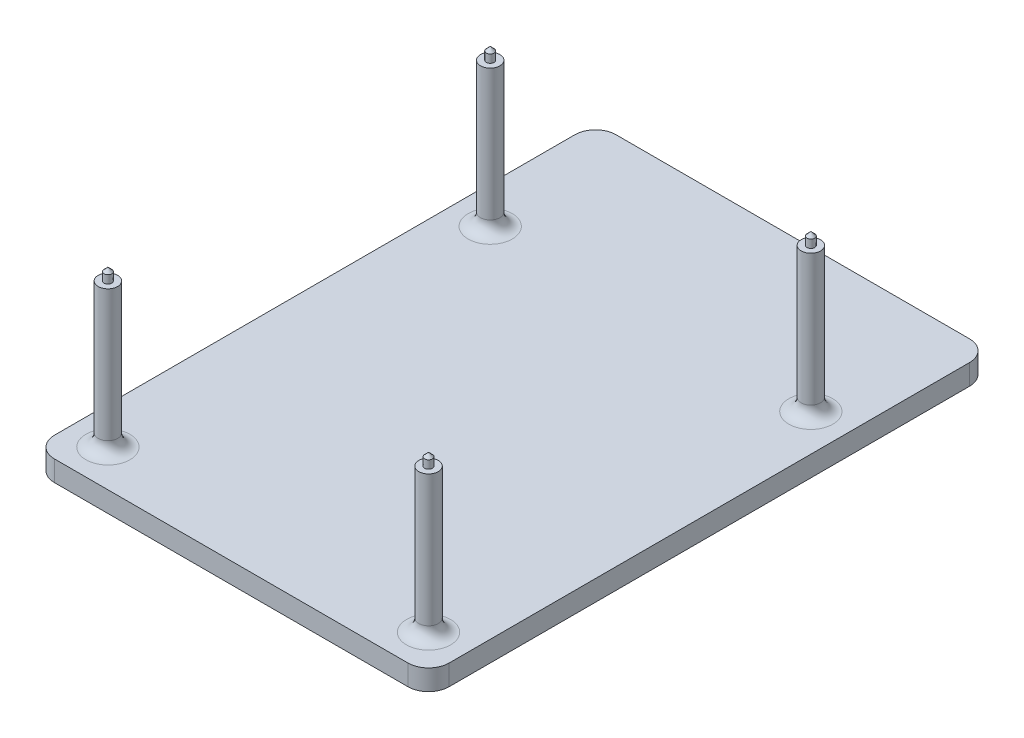
SolidWorks part; units mm, degrees
ref_plane "Front Plane" through (0, 0, 0) normal (0, 0, 1) x (1, 0, 0)
ref_plane "Top Plane" through (0, 0, 0) normal (0, 1, 0) x (1, 0, 0)
ref_plane "Right Plane" through (0, 0, 0) normal (1, 0, 0) x (0, 0, -1)
sketch "Sketch1" plane through (0, 0, 0) normal (0, 1, 0) x (1, 0, 0)
  line L0 (0, 160.782) -> (109.22, 0) construction
  line L1 (5.08, 123.19) -> (104.14, 123.19) construction
  line L2 (5.08, 123.19) -> (5.08, 5.08) construction
  line L3 (5.08, 5.08) -> (104.14, 5.08) construction
  line L4 (104.14, 123.19) -> (104.14, 5.08) construction
  line L5 (0, 0) -> (109.22, 0) construction
  line L6 (0, 0) -> (0, 160.782) construction
  line L7 (0, 160.782) -> (109.22, 160.782) construction
  line L8 (109.22, 0) -> (109.22, 160.782) construction
  line L10 (115.57, 167.132) -> (-6.35, 167.132)
  line L11 (115.57, 167.132) -> (115.57, -6.35)
  line L12 (115.57, -6.35) -> (-6.35, -6.35)
  line L13 (-6.35, 167.132) -> (-6.35, -6.35)
  line L14 (115.57, 167.132) -> (-6.35, -6.35) construction
  line L15 (115.57, -6.35) -> (-6.35, 167.132) construction
  point P9 (54.61, 80.391)
  dimension "D1" = 5.08
  dimension "D2" = 5.08
  dimension "D3" = 104.14
  dimension "D4" = 123.19
  dimension "D5" = 160.782
  dimension "D6" = 109.22
  dimension "D7" = 6.35
  dimension "D8" = 6.35
extrude "Boss-Extrude1" add sketch "Sketch1" along normal blind 6.35
sketch "Sketch2" plane through (0, 6.35, 0) normal (0, 1, 0) x (1, 0, 0)
  circle A0 centre (5.08, 5.08) radius 1.9304 construction
  circle A1 centre (104.14, 5.08) radius 3
  circle A2 centre (104.14, 123.19) radius 3
  circle A3 centre (5.08, 123.19) radius 3
  circle A4 centre (5.08, 5.08) radius 3
  dimension "D1" = 3.8608
  dimension "D2" = 6
extrude "Boss-Extrude2" add sketch "Sketch2" along normal blind 44.45
fillet "Fillet1" radius 6.35 4 edges at (115.57, 3.175, 6.35) (-6.35, 3.175, 6.35) (115.57, 3.175, -167.132) (-6.35, 3.175, -167.132)
fillet "Fillet2" radius 3.81 4 edges at (104.14, 6.35, -8.08) (104.14, 6.35, -126.19) (5.08, 6.35, -126.19) (5.08, 6.35, -8.08)
ref_axis "Axis1" through (5.08, 50.8, -5.08) along (0, -1, 0)
ref_plane "Plane1" through (0, 0, -5.08) normal (0, 0, 1) x (1, 0, 0)
sketch "Sketch3" plane through (0, 0, -5.08) normal (0, 0, 1) x (1, 0, 0)
  line L0 (8.08, 50.8) -> (2.08, 50.8) construction
  line L1 (8.08, 50.8) -> (2.08, 50.8)
  line L2 (5.08, 50.8) -> (5.08, 54.5)
  line L3 (5.08, 54.5) -> (3.88, 53.3)
  line L4 (3.88, 53.3) -> (3.88, 50.8)
  dimension "D1" = 1.2
  dimension "D2" = 45
  dimension "D3" = 2.5
revolve "Revolve1" add sketch "Sketch3" angle 360 about axis through (5.08, 50.8, -5.08) along (0, -1, 0) region at (4.5187, 52.3694, -5.08)
ref_axis "Axis2" through (5.08, 50.8, -123.19) along (0, -1, 0)
ref_axis "Axis3" through (104.14, 50.8, -123.19) along (0, -1, 0)
ref_axis "Axis4" through (104.14, 50.8, -5.08) along (0, -1, 0)
ref_plane "Plane2" through (0, 0, -123.19) normal (0, 0, 1) x (1, 0, 0)
ref_plane "Plane3" through (5.08, 0, 0) normal (-1, 0, 0) x (0, 0, 1)
ref_plane "Plane4" through (104.14, 0, 0) normal (1, 0, 0) x (0, 0, -1)
ref_plane "Plane5" through (54.61, 0, 0) normal (-1, 0, 0) x (0, 0, 1)
ref_plane "Plane6" through (0, 0, -64.135) normal (0, 0, 1) x (1, 0, 0)
mirror "Mirror1" about plane through (0, 0, -64.135) normal (0, 0, 1) of "Revolve1"
mirror "Mirror2" about plane through (54.61, 0, 0) normal (-1, 0, 0) of "Mirror1", "Revolve1"
equation "\"D2@Sketch1\"=\"D1@Sketch1\""
equation "\"D1@Sketch3\"=1.2mm"
